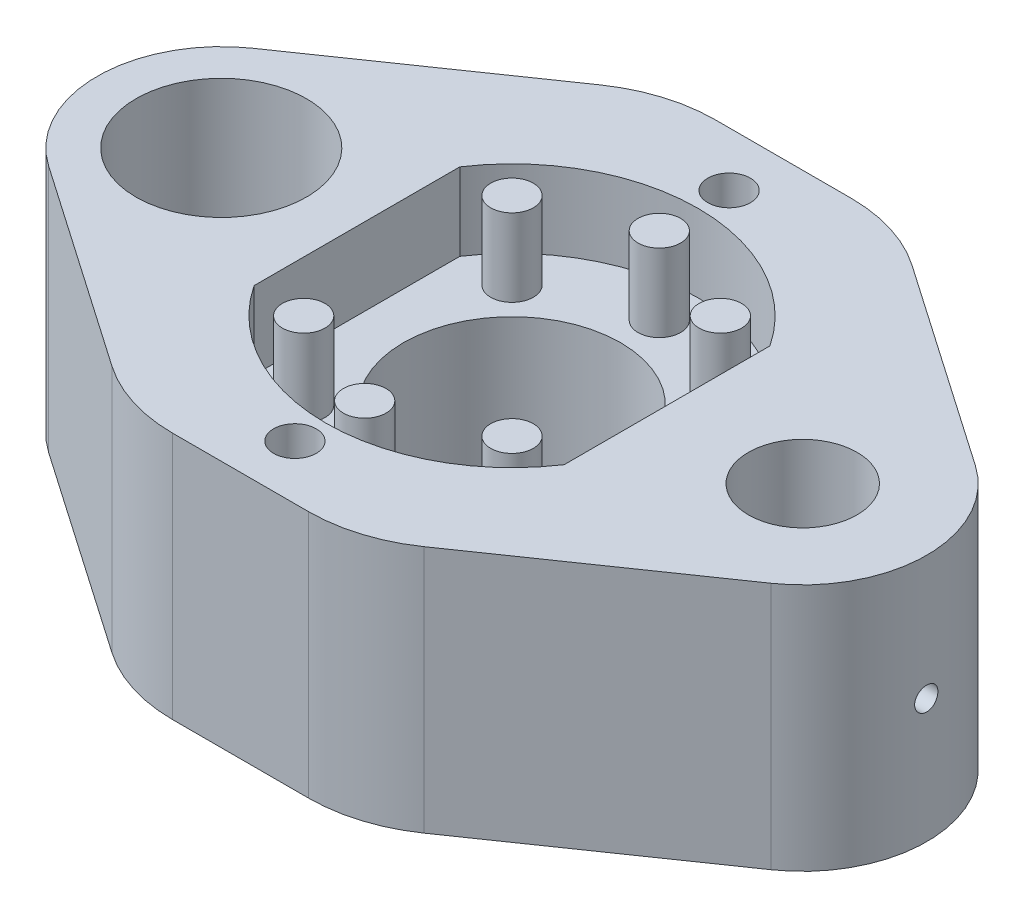
SolidWorks part; units mm, degrees
ref_plane "Front Plane" through (0, 0, 0) normal (0, 0, 1) x (1, 0, 0)
ref_plane "Top Plane" through (0, 0, 0) normal (0, 1, 0) x (1, 0, 0)
ref_plane "Right Plane" through (0, 0, 0) normal (1, 0, 0) x (0, 0, -1)
sketch "Sketch1" plane through (0, 0, 0) normal (0, 1, 0) x (1, 0, 0)
  line L0 (-20, 13.2665) -> (-20, -13.2665)
  line L1 (20, 13.2665) -> (20, -13.2665)
  line L2 (-15, -35) -> (15, -35)
  line L3 (-15, -35) -> (-46.5969, -13.1623)
  line L4 (0, 105.5868) -> (0, -105.5868) construction
  line L5 (15, -35) -> (46.5969, -13.1623)
  line L6 (-86.2788, 0) -> (86.2788, 0) construction
  line L7 (-15, 35) -> (15, 35)
  line L8 (15, 35) -> (46.5969, 13.1623)
  line L9 (-15, 35) -> (-46.5969, 13.1623)
  circle A0 centre (0, 0) radius 14
  arc A1 (-20, -13.2665) -> (20, -13.2665) centre (0, 0) ccw
  arc A2 (20, 13.2665) -> (-20, 13.2665) centre (0, 0) ccw
  arc A3 (-46.5969, 13.1623) -> (-46.5969, -13.1623) centre (-37.5, 0) ccw
  circle A4 centre (-37.5, 0) radius 11
  circle A5 centre (37.5, 0) radius 7
  arc A6 (46.5969, 13.1623) -> (46.5969, -13.1623) centre (37.5, 0) cw
  point P13 (0, -35)
  point P16 (0, 0)
  point P24 (0, 0)
  dimension "D1" = 28
  dimension "D2" = 48
  dimension "D4" = 22
  dimension "D5" = 32
  dimension "D9" = 14
  dimension "D3" = 40
  dimension "D6" = 37.5
  dimension "D7" = 30
  dimension "D8" = 35
extrude "Extrude2" add sketch "Sketch1" along normal blind 32 contours A6 L8 L7 L9 A3 L3 L2 L5 A2 L1 A1 L0 A4 region at (-30.0715, 0, 23.0293)
extrude "Extrude3" add sketch "Sketch" along normal offset from surface (22 mm away) 10 contours L1 A2 L0 A1 A0 region at (0, 0, -23.3752) up to face at (0, 32, 0)
sketch "Sketch" plane through (0, 0, 0) normal (0, 1, 0) x (1, 0, 0) same geometry as "Sketch1"
fillet "Fillet1" radius 20 4 edges at (-15, 16, -35) (15, 16, -35) (15, 16, 35) (-15, 16, 35)
sketch "Sketch5" plane through (0, 22, 0) normal (0, 1, 0) x (1, 0, 0)
  circle A0 centre (13.435, 13.435) radius 2.75
  circle A1 centre (13.435, 13.435) radius 2.75 construction
  point P3 (0, 0)
  point P4 (0, 0)
  dimension "D1" = 5.5
extrude "Extrude5" add sketch "Sketch5" along normal up to surface (10 mm away) up to face at (0, 32, 0)
pattern_circular "CirPattern1" count 3 every 45 about axis through (0, 22, 0) along (0, 1, 0) of "Extrude5"
mirror "Mirror1" about plane through (0, 0, 0) normal (0, 0, 1) of "Extrude5", "CirPattern1"
sketch3d "3DSketch3"
  circle A0 centre (37.5, 16, 0) radius 8
  circle A1 centre (37.5, 16, 0) radius 1.5
  circle A2 centre (37.5, 32, 0) radius 7 construction
  point P3 (37.5, 39, 0)
  point P5 (39, 16, 0)
  point P7 (37.5, 24, 0)
  dimension "D1" = 16
  dimension "D2" = 16
  dimension "D3" = 3
extrude "Extrude10" cut sketch "3DSketch3" along direction (0, 1, 0) on the side against the normal mid plane 3 contours A0
extrude "Extrude11" cut sketch "Sketch" along direction (1, 0, 0) on the side of the normal through all contours A1
sketch3d "Sketch" same geometry as "3DSketch3"
hole_wizard "M5 Clearance Hole1" positions "Sketch6" profile "Sketch7" hole size "M5" standard "ISO" end condition through all
sketch "Sketch6" plane through (0, 32, 0) normal (0, 1, 0) x (1, 0, 0)
  point P0 (0, 28)
  point P3 (0, -28)
  point P4 (0, 0)
  point P9 (0, 0)
  point P12 (0, 0)
  point P13 (0, 0)
  point P18 (0, 0)
  point P21 (0, 0)
sketch "Sketch7" plane through (0, 32, -28) normal (1, 0, 0) x (0, 0, 1)
  line L0 (0, 0) -> (0, 32)
  line L1 (0, 32) -> (2.75, 32)
  line L2 (2.75, 32) -> (2.75, 0)
  line L5 (2.75, 0) -> (0, 0)
  line L11 (0, -6.35) -> (0, 107.95) construction
  dimension "Thru Hole Dia." = 5.5
  dimension "Thru Hole Depth" = 32
